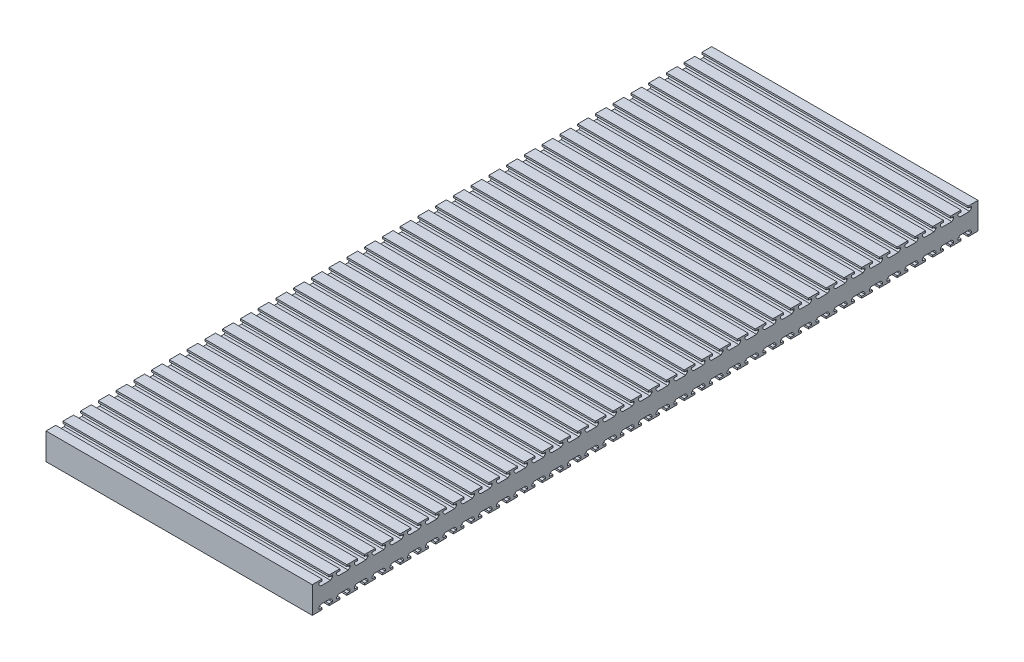
SolidWorks part; units mm, degrees
ref_plane "Frontal" through (0, 0, 0) normal (0, 0, 1) x (1, 0, 0)
ref_plane "Superior" through (0, 0, 0) normal (0, 1, 0) x (1, 0, 0)
ref_plane "Direito" through (0, 0, 0) normal (1, 0, 0) x (0, 0, -1)
sketch "Esboço1" plane through (0, 0, 0) normal (0, 0, 1) x (1, 0, 0)
  line L1 (-150, 15) -> (150, 15)
  line L2 (-150, 15) -> (-150, -15)
  line L3 (-150, -15) -> (150, -15)
  line L4 (150, 15) -> (150, -15)
  line L5 (-150, 15) -> (150, -15) construction
  line L6 (-150, -15) -> (150, 15) construction
  point P0 (0, 0)
  dimension "D1" = 300
  dimension "D2" = 30
extrude "Ressalto-extrusão1" add sketch "Esboço1" along normal mid plane 750
sketch "Esboço2" plane through (150, 0, 0) normal (1, 0, 0) x (0, 0, -1)
  line L0 (-364, 15) -> (-364, 13)
  line L1 (-375, 15) -> (375, 15) construction
  line L2 (-364, 13) -> (-367.5, 13)
  line L3 (-367.5, 13) -> (-367.5, 11)
  line L4 (-367.5, 11) -> (-365.5, 9)
  line L5 (-365.5, 9) -> (-354.5, 9)
  line L6 (-354.5, 9) -> (-352.5, 11)
  line L7 (-352.5, 11) -> (-352.5, 13)
  line L8 (-352.5, 13) -> (-356, 13)
  line L9 (-356, 13) -> (-356, 15)
  line L10 (-356, 15) -> (-364, 15)
  line L11 (-360, 15) -> (-360, 9) construction
  line L12 (-375, -15) -> (-375, 15) construction
  dimension "D1" = 8
  dimension "D2" = 15
  dimension "D3" = 2
  dimension "D4" = 2
  dimension "D5" = 45
  dimension "D6" = 2
  dimension "D7" = 3.5
  dimension "D8" = 15
extrude "Corte-extrusão1" cut sketch "Esboço2" against normal through all
pattern_linear "Padrão linear1" count 37 spacing 20 along (0, 0, -1) of "Corte-extrusão1"
mirror "Espelhar1" about plane through (0, 0, 0) normal (0, 1, 0) of "Padrão linear1"
